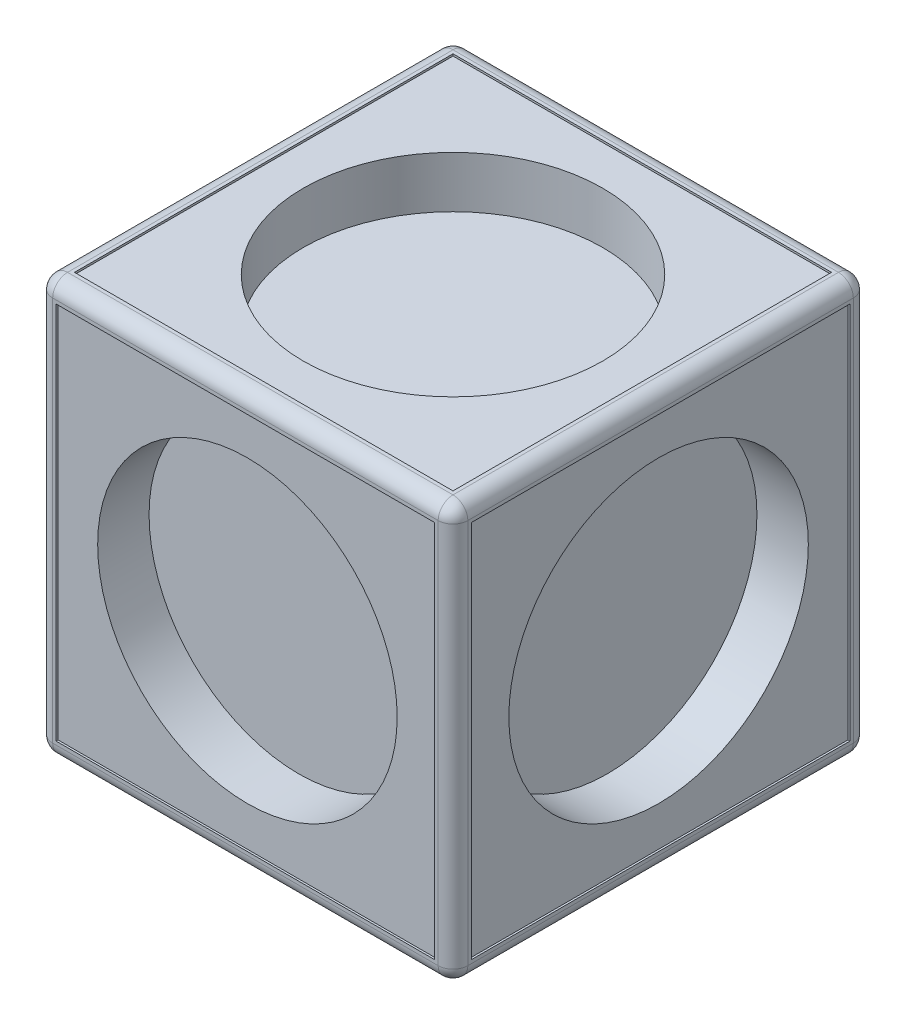
SolidWorks part; units mm, degrees
ref_plane "Front Plane" through (0, 0, 0) normal (0, 0, 1) x (1, 0, 0)
ref_plane "Top Plane" through (0, 0, 0) normal (0, 1, 0) x (1, 0, 0)
ref_plane "Right Plane" through (0, 0, 0) normal (1, 0, 0) x (0, 0, -1)
sketch "Sketch2" plane through (0, 0, 0) normal (0, 0, 1) x (1, 0, 0)
  line L1 (21, 21) -> (-21, 21)
  line L2 (21, 21) -> (21, -21)
  line L3 (21, -21) -> (-21, -21)
  line L4 (-21, 21) -> (-21, -21)
  line L5 (21, 21) -> (-21, -21) construction
  line L6 (21, -21) -> (-21, 21) construction
  point P0 (0, 0)
  dimension "D2" = 42
  dimension "D3" = 42
extrude "Boss-Extrude1" add sketch "Sketch2" along normal blind 42
sketch "Sketch3" plane through (0, 21, 0) normal (0, 1, 0) x (1, 0, 0)
  line L0 (21, -42) -> (-21, -42) construction
  line L1 (-21, -42) -> (21, -42)
  line L2 (-21, -42) -> (-21, 0)
  line L3 (-21, 0) -> (21, 0)
  line L4 (21, -42) -> (21, 0)
  line L5 (-21, -42) -> (-21, 0) construction
  circle A0 centre (0, -21) radius 15.15
  dimension "D1" = 30.3
  dimension "D2" = 21
  dimension "D3" = 21
extrude "Cut-Extrude2" cut sketch "Sketch3" against normal blind 5.4 contours A0 | A0 region at (0, 21, 21)
sketch "Sketch4" plane through (0, 21, 0) normal (0, 1, 0) x (1, 0, 0)
  line L1 (-19.15, -40.15) -> (19.15, -40.15)
  line L2 (-19.15, -40.15) -> (-19.15, -1.85)
  line L3 (-19.15, -1.85) -> (19.15, -1.85)
  line L4 (19.15, -40.15) -> (19.15, -1.85)
  line L5 (-19.15, -40.15) -> (19.15, -1.85) construction
  line L6 (-19.15, -1.85) -> (19.15, -40.15) construction
  point P0 (0, -21)
  dimension "D1" = 38.3
  dimension "D2" = 38.3
extrude "Cut-Extrude3" cut sketch "Sketch4" against normal blind 0.2
mirror "Mirror1" about plane through (0, 0, 0) normal (0, 1, 0) of "Cut-Extrude3", "Cut-Extrude2"
sketch "Sketch5" plane through (21, 0, 0) normal (1, 0, 0) x (0, 0, -1)
  line L0 (-42, 21) -> (0, 21) construction
  line L1 (0, -21) -> (0, 21) construction
  circle A0 centre (-21, 0) radius 15.15
  dimension "D1" = 30.3
  dimension "D2" = 21
  dimension "D3" = 21
extrude "Cut-Extrude4" cut sketch "Sketch5" against normal blind 5.4
sketch "Sketch6" plane through (21, 0, 0) normal (1, 0, 0) x (0, 0, -1)
  line L1 (-1.85, 19.15) -> (-40.15, 19.15)
  line L2 (-1.85, 19.15) -> (-1.85, -19.15)
  line L3 (-1.85, -19.15) -> (-40.15, -19.15)
  line L4 (-40.15, 19.15) -> (-40.15, -19.15)
  line L5 (-1.85, 19.15) -> (-40.15, -19.15) construction
  line L6 (-1.85, -19.15) -> (-40.15, 19.15) construction
  point P0 (-21, 0)
  dimension "D1" = 38.3
  dimension "D2" = 38.3
extrude "Cut-Extrude5" cut sketch "Sketch6" against normal blind 0.2
sketch "Sketch7" plane through (0, 0, 42) normal (0, 0, 1) x (1, 0, 0)
  circle A0 centre (0, 0) radius 15.15
  dimension "D1" = 30.3
extrude "Cut-Extrude6" cut sketch "Sketch7" against normal blind 5.4
sketch "Sketch8" plane through (0, 0, 42) normal (0, 0, 1) x (1, 0, 0)
  line L1 (19.15, 19.15) -> (-19.15, 19.15)
  line L2 (19.15, 19.15) -> (19.15, -19.15)
  line L3 (19.15, -19.15) -> (-19.15, -19.15)
  line L4 (-19.15, 19.15) -> (-19.15, -19.15)
  line L5 (19.15, 19.15) -> (-19.15, -19.15) construction
  line L6 (19.15, -19.15) -> (-19.15, 19.15) construction
  point P0 (0, 0)
  dimension "D1" = 38.3
  dimension "D2" = 38.3
extrude "Cut-Extrude7" cut sketch "Sketch8" against normal blind 0.2
mirror "Mirror2" about plane through (0, 0, 0) normal (1, 0, 0) of "Cut-Extrude5", "Cut-Extrude4"
ref_plane "Plane1" through (0, 0, 21) normal (0, 0, -1) x (-1, 0, 0)
mirror "Mirror3" about plane through (0, 0, 21) normal (0, 0, -1) of "Cut-Extrude7", "Cut-Extrude6"
fillet "Fillet1" radius 1.5 12 edges at (21, -21, 21) (0, -21, 0) (-21, -21, 21) (-21, 0, 42) (0, -21, 42) (0, 21, 42) (21, 0, 42) (21, 21, 21) (21, 0, 0) (-21, 0, 0) (0, 21, 0) (-21, 21, 21)
